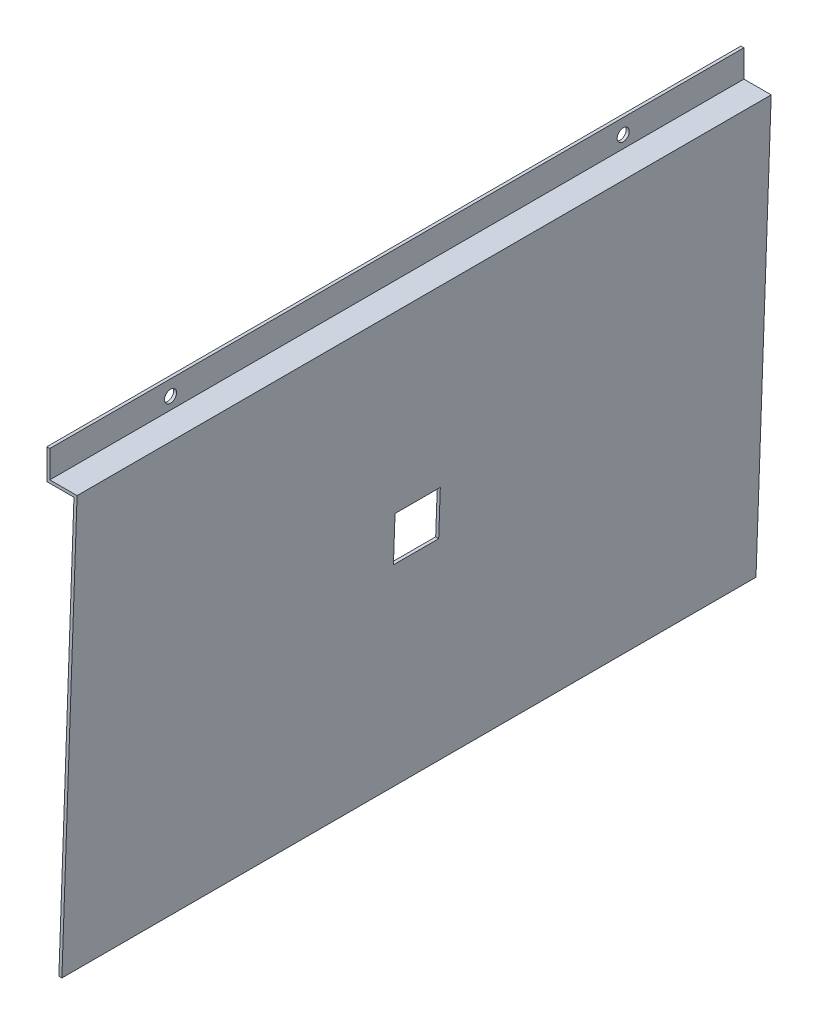
SolidWorks part; units mm, degrees
ref_plane "Alzado" through (0, 0, 0) normal (0, 0, 1) x (1, 0, 0)
ref_plane "Planta" through (0, 0, 0) normal (0, 1, 0) x (1, 0, 0)
ref_plane "Vista lateral" through (0, 0, 0) normal (1, 0, 0) x (0, 0, -1)
sketch "Croquis1" plane through (0, 0, 0) normal (0, 0, 1) x (1, 0, 0)
  line L0 (-38.1189, 44.5866) -> (-38.1189, 34.5866)
  line L1 (-38.1189, 34.5866) -> (-29.1189, 34.5866)
  line L2 (-29.1189, 34.5866) -> (-34.1209, -105.324)
extrude "Extruir-Lámina1" add sketch "Croquis1" along normal blind 230 thin thin type one direction reverse wall 1
sketch "Croquis2" plane through (-37.1189, 0, 0) normal (1, 0, 0) x (0, 0, -1)
  line L0 (0, 44.5866) -> (0, 34.5866) construction
  line L1 (-230, 44.5866) -> (0, 44.5866) construction
  line L2 (-230, 44.5866) -> (-230, 35.5866) construction
  circle A0 centre (-190, 39.5866) radius 2
  circle A1 centre (-40, 39.5866) radius 2
  point P4 (0, 39.5866)
  dimension "D1" = 40
  dimension "D2" = 5
  dimension "D3" = 5
  dimension "D4" = 40
extrude "Cortar-Extruir1" cut sketch "Croquis2" against normal up to surface (1 mm away) up to face at (-38.1189, 39.5866, 115)
sketch "Croquis3" plane through (-29.3173, 1.0481, 0) normal (0.9994, -0.0357, 0) x (0, 0, -1)
  line L0 (-230, 34.5606) -> (0, 34.5606) construction
  line L1 (-122.5, -40.4394) -> (-107.5, -40.4394)
  line L2 (-122.5, -40.4394) -> (-122.5, -25.4394)
  line L3 (-122.5, -25.4394) -> (-107.5, -25.4394)
  line L4 (-107.5, -40.4394) -> (-107.5, -25.4394)
  line L5 (-122.5, -40.4394) -> (-107.5, -25.4394) construction
  line L6 (-122.5, -25.4394) -> (-107.5, -40.4394) construction
  line L8 (0, 34.5606) -> (0, -106.4758) construction
  point P0 (-115, -32.9394)
  point P7 (0, -35.9576)
  dimension "D1" = 60
  dimension "D2" = 115
extrude "Cortar-Extruir2" cut sketch "Croquis3" against normal up to surface (1 mm away) up to face at (-31.6199, -35.3687, 115)
